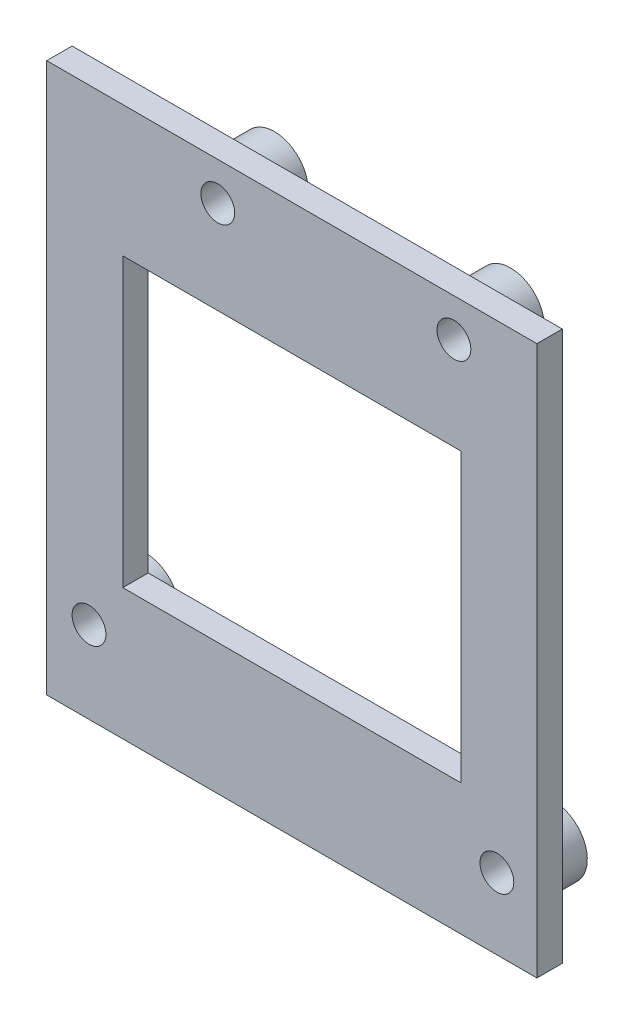
SolidWorks part; units mm, degrees
ref_plane "Plan de face" through (0, 0, 0) normal (0, 0, 1) x (1, 0, 0)
ref_plane "Plan de dessus" through (0, 0, 0) normal (0, 1, 0) x (1, 0, 0)
ref_plane "Plan de droite" through (0, 0, 0) normal (1, 0, 0) x (0, 0, -1)
sketch "Esquisse1" plane through (0, 0, 0) normal (0, 0, 1) x (1, 0, 0)
  line L1 (-29, 32.5) -> (29, 32.5)
  line L2 (-29, 32.5) -> (-29, -32.5)
  line L3 (-29, -32.5) -> (29, -32.5)
  line L4 (29, 32.5) -> (29, -32.5)
  line L5 (-29, 32.5) -> (29, -32.5) construction
  line L6 (-29, -32.5) -> (29, 32.5) construction
  point P0 (0, 0)
  dimension "D1" = 65
  dimension "D2" = 58
base flange "Tôle de base pliée1" sketch "Esquisse1" thickness 3 reverse thickness direction no parameters "D1"=2
sketch "Esquisse6" plane through (0, 0, 0) normal (0, 0, 1) x (1, 0, 0)
  circle A0 centre (-8.76, 28) radius 2
  circle A1 centre (19.18, 28) radius 2
  circle A2 centre (-24, -22.8) radius 2
  circle A3 centre (24.26, -24.07) radius 2
  dimension "D7" = 4
  dimension "D8" = 4
  dimension "D9" = 4
  dimension "D10" = 4
  dimension "D1" = 27.94
  dimension "D2" = 50.8
  dimension "D3" = 52.07
  dimension "D4" = 48.26
  dimension "D5" = 28
  dimension "D12" = 15.24
  dimension "D6" = 24
extrude "Enlèv. mat.-Extru.1" cut sketch "Esquisse6" against normal up to next normal cut yes
sketch "Esquisse7" plane through (0, 0, 0) normal (0, 0, 1) x (1, 0, 0)
  line L0 (0, 21.25) -> (0, -26.25) construction
  circle A0 centre (-17, -26.25) radius 2
  circle A1 centre (0, -26.25) radius 2
  circle A2 centre (17, -26.25) radius 2
  circle A3 centre (0, 21.25) radius 2
  circle A4 centre (17, 21.25) radius 2
  circle A5 centre (-17, 21.25) radius 2
  circle A7 centre (24.26, -24.07) radius 2 construction
  point P3 (0, -2.5)
  dimension "D1" = 4
  dimension "D4" = 34
  dimension "D5" = 47.5
  dimension "D6" = 2.5
  dimension "D2" = 3
  dimension "D3" = 2
extrude "Enlèv. mat.-Extru.2" cut sketch "Esquisse7" against normal up to next normal cut yes
sketch "Esquisse8" plane through (0, 0, -3) normal (0, 0, 1) x (1, 0, 0)
  circle A0 centre (-8.76, 28) radius 4
  circle A1 centre (19.18, 28) radius 4
  circle A2 centre (24.26, -24.07) radius 4
  circle A3 centre (-24, -22.8) radius 4
  circle A4 centre (-8.76, 28) radius 2 construction
  circle A5 centre (19.18, 28) radius 2 construction
  circle A7 centre (-24, -22.8) radius 2 construction
  circle A8 centre (-8.76, 28) radius 2
  circle A9 centre (19.18, 28) radius 2
  circle A10 centre (24.26, -24.07) radius 2
  circle A11 centre (-24, -22.8) radius 2
  dimension "D1" = 8
  dimension "D2" = 8
  dimension "D4" = 8
extrude "Boss.-Extru.1" add sketch "Esquisse8" against normal blind 2.7
sketch "Esquisse11" plane through (0, 0, -5.7) normal (0, 0, -1) x (-1, 0, 0)
  circle A0 centre (24, -22.8) radius 4 construction
  circle A1 centre (8.76, 28) radius 4 construction
  circle A2 centre (-24.26, -24.07) radius 4 construction
  circle A3 centre (-19.18, 28) radius 4 construction
  circle A4 centre (24, -22.8) radius 4
  circle A5 centre (8.76, 28) radius 4
  circle A6 centre (-24.26, -24.07) radius 4
  circle A7 centre (-19.18, 28) radius 4
extrude "Boss.-Extru.3" add sketch "Esquisse11" along normal blind 1
sketch "Esquisse9" plane through (0, 0, 0) normal (0, 0, 1) x (1, 0, 0)
  line L1 (-20, 17) -> (20, 17)
  line L2 (-20, 17) -> (-20, -17)
  line L3 (-20, -17) -> (20, -17)
  line L4 (20, 17) -> (20, -17)
  line L5 (-20, 17) -> (20, -17) construction
  line L6 (-20, -17) -> (20, 17) construction
  point P0 (0, 0)
  dimension "D1" = 40
  dimension "D2" = 34
extrude "Enlèv. mat.-Extru.3" cut sketch "Esquisse9" against normal up to next normal cut yes
sketch "Esquisse10" plane through (0, 0, 0) normal (0, 0, 1) x (1, 0, 0)
  circle A0 centre (24.26, -24.07) radius 1.4
  point P0 (24.26, -24.07)
  dimension "D1" = 2.8
extrude "Boss.-Extru.2" [suppressed] add sketch "Esquisse10" along normal blind 10
sketch "Esquisse12" plane through (0, 0, -3) normal (0, 0, -1) x (-1, 0, 0)
  circle A0 centre (-17, 21.25) radius 4
  circle A1 centre (0, 21.25) radius 4
  circle A2 centre (17, 21.25) radius 4
  circle A3 centre (17, -26.25) radius 4
  circle A4 centre (0, -26.25) radius 4
  circle A5 centre (-17, -26.25) radius 4
  circle A6 centre (-17, -26.25) radius 2 construction
  circle A7 centre (0, -26.25) radius 2 construction
  circle A8 centre (17, -26.25) radius 2 construction
  circle A9 centre (17, 21.25) radius 2 construction
  circle A10 centre (0, 21.25) radius 2 construction
  circle A11 centre (-17, 21.25) radius 2 construction
  circle A12 centre (-17, -26.25) radius 2
  circle A13 centre (0, -26.25) radius 2
  circle A14 centre (17, -26.25) radius 2
  circle A15 centre (17, 21.25) radius 2
  circle A16 centre (0, 21.25) radius 2
  circle A17 centre (-17, 21.25) radius 2
  dimension "D1" = 8
  dimension "D2" = 8
  dimension "D4" = 8
  dimension "D3" = 8
  dimension "D5" = 8
  dimension "D6" = 8
extrude "Boss.-Extru.4" add sketch "Esquisse12" along normal blind 3.7
sketch "Esquisse13" plane through (0, 0, 0) normal (0, 0, 1) x (1, 0, 0)
  circle A0 centre (-17, 21.25) radius 2 construction
  circle A1 centre (-17, -26.25) radius 2 construction
  circle A2 centre (0, 21.25) radius 2 construction
  circle A3 centre (0, -26.25) radius 2 construction
  circle A4 centre (17, -26.25) radius 2 construction
  circle A5 centre (17, 21.25) radius 2 construction
  circle A6 centre (-17, 21.25) radius 2
  circle A7 centre (-17, -26.25) radius 2
  circle A8 centre (0, 21.25) radius 2
  circle A9 centre (0, -26.25) radius 2
  circle A10 centre (17, -26.25) radius 2
  circle A11 centre (17, 21.25) radius 2
extrude "Boss.-Extru.5" add sketch "Esquisse13" against normal blind 1
sketch "Lignes de pliage1" [suppressed] plane through (0, 0, 0) normal (0, 1, 0) x (1, 0, 0)
sketch "Cube de visualisation1" [suppressed] plane through (0, 0, 0) normal (0, 1, 0) x (1, 0, 0)
sheet metal parameters "Tôlerie1" thickness 3 parameters "D1"=2
flat pattern "Etat déplié1" [suppressed]
sketch "Lignes de pliage2" plane through (0, 0, 0) normal (0, 1, 0) x (1, 0, 0)
sketch3d "Cube de visualisation2" [suppressed]
  line L0 (-35, -35, 0) -> (35, -35, 0) construction
  line L1 (-35, 35, 0) -> (35, 35, 0) construction
  line L2 (-35, -35, 0) -> (-35, 35, 0) construction
  line L3 (35, -35, 0) -> (35, 35, 0) construction
sheet metal parameters "Tôlerie2" thickness 3 parameters "D1"=2
flat pattern "Etat déplié1"
sketch "Lignes de pliage2" plane through (0, 0, 0) normal (0, 1, 0) x (1, 0, 0)
sketch3d "Cube de visualisation2" [suppressed]
  line L0 (29, 32.5, 0) -> (29, -32.5, 0) construction
  line L1 (-29, 32.5, 0) -> (-29, -32.5, 0) construction
  line L2 (29, 32.5, 0) -> (-29, 32.5, 0) construction
  line L3 (29, -32.5, 0) -> (-29, -32.5, 0) construction
sheet metal parameters "Tôlerie3" thickness 3 parameters "D1"=2
flat pattern "Etat déplié1"
sketch "Lignes de pliage2" plane through (0, 0, 0) normal (0, 1, 0) x (1, 0, 0)
sketch3d "Cube de visualisation2" [suppressed]
  line L0 (29, 32.5, 0) -> (29, -32.5, 0) construction
  line L1 (-29, 32.5, 0) -> (-29, -32.5, 0) construction
  line L2 (29, 32.5, 0) -> (-29, 32.5, 0) construction
  line L3 (29, -32.5, 0) -> (-29, -32.5, 0) construction
sheet metal parameters "Tôlerie4" thickness 3 parameters "D1"=2
flat pattern "Etat déplié1"
sketch "Lignes de pliage2" plane through (0, 0, 0) normal (0, 1, 0) x (1, 0, 0)
sketch3d "Cube de visualisation2" [suppressed]
  line L0 (29, 32.5, 0) -> (29, -32.5, 0) construction
  line L1 (-29, 32.5, 0) -> (-29, -32.5, 0) construction
  line L2 (29, 32.5, 0) -> (-29, 32.5, 0) construction
  line L3 (29, -32.5, 0) -> (-29, -32.5, 0) construction
sheet metal parameters "Tôlerie5" thickness 3 parameters "D1"=2
flat pattern "Etat déplié1"
sketch "Lignes de pliage2" plane through (0, 0, 0) normal (0, 1, 0) x (1, 0, 0)
sketch3d "Cube de visualisation2" [suppressed]
  line L0 (29, 32.5, 0) -> (29, -32.5, 0) construction
  line L1 (-29, 32.5, 0) -> (-29, -32.5, 0) construction
  line L2 (29, 32.5, 0) -> (-29, 32.5, 0) construction
  line L3 (29, -32.5, 0) -> (-29, -32.5, 0) construction
sheet metal parameters "Tôlerie6" thickness 3 parameters "D1"=2
flat pattern "Etat déplié1"
sketch "Lignes de pliage2" plane through (0, 0, 0) normal (0, 1, 0) x (1, 0, 0)
sketch3d "Cube de visualisation2" [suppressed]
  line L0 (29, 32.5, 0) -> (29, -32.5, 0) construction
  line L1 (-29, 32.5, 0) -> (-29, -32.5, 0) construction
  line L2 (29, 32.5, 0) -> (-29, 32.5, 0) construction
  line L3 (29, -32.5, 0) -> (-29, -32.5, 0) construction
sheet metal parameters "Tôlerie7" thickness 3 parameters "D1"=2
flat pattern "Etat déplié1"
sketch "Lignes de pliage2" plane through (0, 0, 0) normal (0, 1, 0) x (1, 0, 0)
sketch3d "Cube de visualisation2" [suppressed]
  line L0 (29, 32.5, 0) -> (29, -32.5, 0) construction
  line L1 (-29, 32.5, 0) -> (-29, -32.5, 0) construction
  line L2 (29, 32.5, 0) -> (-29, 32.5, 0) construction
  line L3 (29, -32.5, 0) -> (-29, -32.5, 0) construction
sheet metal parameters "Tôlerie8" thickness 3 parameters "D1"=2
flat pattern "Etat déplié1"
sketch "Lignes de pliage2" plane through (0, 0, 0) normal (0, 1, 0) x (1, 0, 0)
sketch3d "Cube de visualisation2" [suppressed]
  line L0 (29, 32.5, 0) -> (29, -32.5, 0) construction
  line L1 (-29, 32.5, 0) -> (-29, -32.5, 0) construction
  line L2 (29, 32.5, 0) -> (-29, 32.5, 0) construction
  line L3 (29, -32.5, 0) -> (-29, -32.5, 0) construction
sheet metal parameters "Tôlerie9" thickness 3 parameters "D1"=2
flat pattern "Etat déplié1"
sketch "Lignes de pliage2" plane through (0, 0, 0) normal (0, 1, 0) x (1, 0, 0)
sketch3d "Cube de visualisation2" [suppressed]
  line L0 (29, 32.5, 0) -> (29, -32.5, 0) construction
  line L1 (-29, 32.5, 0) -> (-29, -32.5, 0) construction
  line L2 (29, 32.5, 0) -> (-29, 32.5, 0) construction
  line L3 (29, -32.5, 0) -> (-29, -32.5, 0) construction
equation "\"D8@Esquisse6\"=\"D7@Esquisse6\""
equation "\"D9@Esquisse6\"=\"D7@Esquisse6\""
equation "\"D10@Esquisse6\"=\"D7@Esquisse6\""
equation "\"D2@Esquisse8\"=\"D1@Esquisse8\""
equation "\"D4@Esquisse8\"=\"D1@Esquisse8\""
equation "\"D2@Esquisse12\"=\"D1@Esquisse12\""
equation "\"D3@Esquisse12\"=\"D1@Esquisse12\""
equation "\"D4@Esquisse12\"=\"D1@Esquisse12\""
equation "\"D5@Esquisse12\"=\"D1@Esquisse12\""
equation "\"D6@Esquisse12\"=\"D1@Esquisse12\""
